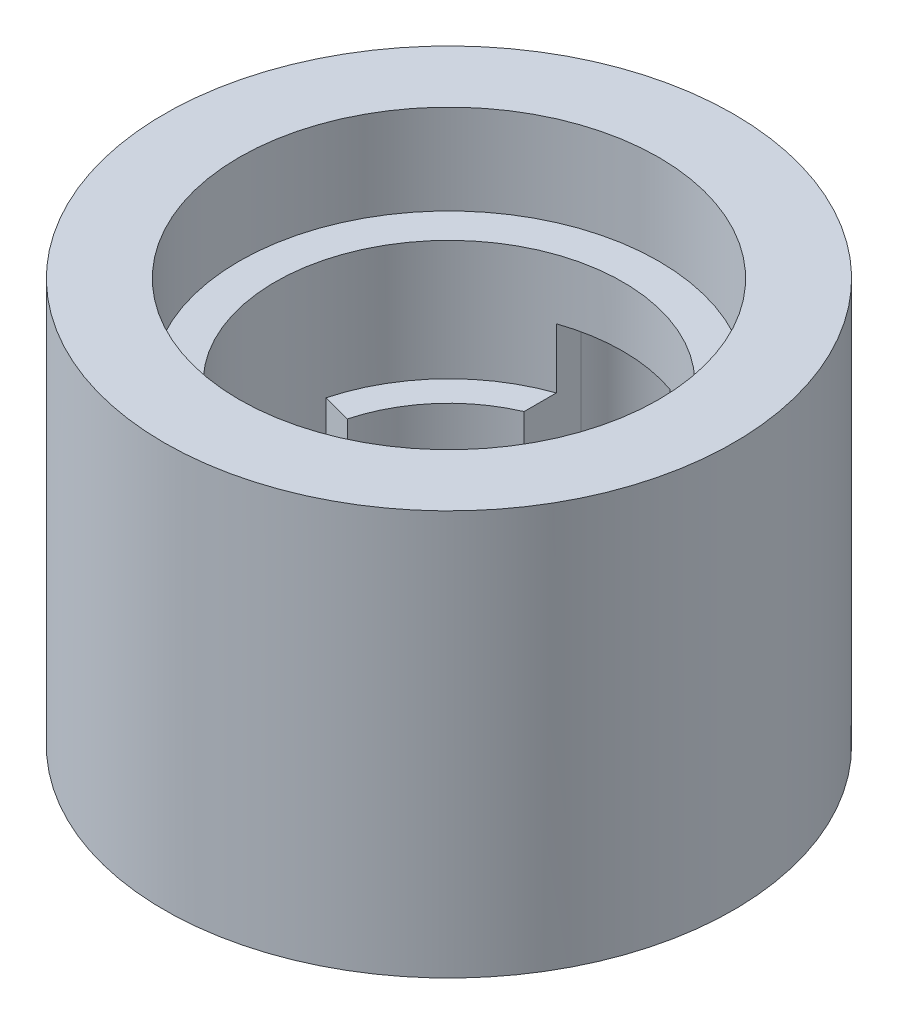
SolidWorks part; units mm, degrees
ref_plane "Front Plane" through (0, 0, 0) normal (0, 0, 1) x (1, 0, 0)
ref_plane "Top Plane" through (0, 0, 0) normal (0, 1, 0) x (1, 0, 0)
ref_plane "Right Plane" through (0, 0, 0) normal (1, 0, 0) x (0, 0, -1)
sketch "Sketch1" plane through (0, 0, 0) normal (0, 1, 0) x (1, 0, 0)
  circle A0 centre (0, 0) radius 12.065
  circle A1 centre (0, 0) radius 7.62
  circle A2 centre (0, 0) radius 6.096
  dimension "D1" = 15.24
  dimension "D2" = 12.192
  dimension "D3" = 24.13
extrude "Boss-Extrude1" add sketch "Sketch1" along normal blind 10.16 contours A1 A2 region at (-7.4045, 0, 0)
extrude "Boss-Extrude2" add sketch "Sketch1<4>" along normal blind 12.7 contours A0 A1 region at (-11.7238, 0, 0)
sketch "Sketch1<4>" plane through (0, 0, 0) normal (0, 1, 0) x (1, 0, 0) same geometry as "Sketch1"
sketch "Sketch9" plane through (0, 12.7, 0) normal (0, 1, 0) x (1, 0, 0)
  circle A0 centre (0, 0) radius 7.62
  circle A1 centre (0, 0) radius 12.065
  circle A2 centre (0, 0) radius 7.62 construction
  circle A3 centre (0, 0) radius 12.065 construction
extrude "Boss-Extrude22" add sketch "Sketch9" along normal blind 1.27
sketch "Sketch10" plane through (0, 13.97, 0) normal (0, 1, 0) x (1, 0, 0)
  circle A0 centre (0, 0) radius 7.62
  circle A1 centre (0, 0) radius 7.62 construction
  circle A2 centre (0, 0) radius 8.89
  dimension "D1" = 1.27
extrude "Cut-Extrude5" cut sketch "Sketch10" against normal up to surface (3.81 mm away) up to face at (0, 10.16, 6.096)
sketch "Sketch14" plane through (0, 0, 0) normal (0, -1, 0) x (1, 0, 0)
  line L0 (6.096, 0) -> (-6.096, 0) construction
  line L1 (2.413, 0) -> (-2.413, 0)
  line L2 (2.413, 0) -> (2.413, -8.001)
  line L3 (2.413, -8.001) -> (-2.413, -8.001)
  line L4 (-2.413, 0) -> (-2.413, -8.001)
  line L5 (0, 0) -> (0, -6.096) construction
  circle A0 centre (0, 0) radius 6.096 construction
  point P4 (0, 0)
  point P10 (0, 0)
  dimension "D1" = 4.826
  dimension "D2" = 1.905
extrude "Cut-Extrude8" cut sketch "Sketch14" against normal offset from surface (7.62 mm away) 2.54 up to face at (0, 10.16, 6.096)
sketch "Sketch15" plane through (0, 7.62, 0) normal (0, -1, 0) x (1, 0, 0)
  line L0 (0, -7.5843) -> (0, -10.033) construction
  line L1 (-2.413, -8.001) -> (2.413, -8.001) construction
  line L2 (2.413, -8.001) -> (-2.413, -8.001)
  arc A0 (2.413, -8.001) -> (-2.413, -8.001) centre (0, -7.5843) cw
  dimension "D1" = 2.032
extrude "Cut-Extrude9" cut sketch "Sketch15" along normal blind 5.08
sketch "Sketch16" plane through (0, 0, 0) normal (0, -1, 0) x (1, 0, 0)
  line L0 (2.413, -5.5981) -> (2.413, -8.001)
  line L1 (2.413, -8.001) -> (-2.413, -8.001)
  line L2 (-2.413, -8.001) -> (-2.413, -5.5981)
  circle A0 centre (0, 0) radius 12.065
  circle A1 centre (0, 0) radius 12.065 construction
  arc A2 (-2.413, -5.5981) -> (2.413, -5.5981) centre (0, 0) cw
  arc A3 (2.413, -5.5981) -> (-2.413, -5.5981) centre (0, 0) ccw construction
extrude "Boss-Extrude24" add sketch "Sketch16" along normal blind 3.175
sketch "Sketch17" plane through (0, 10.16, 0) normal (0, 1, 0) x (1, 0, 0)
  circle A0 centre (0, 0) radius 6.096
  circle A1 centre (0, 0) radius 6.096 construction
  circle A2 centre (0, 0) radius 7.366
  dimension "D1" = 1.27
extrude "Cut-Extrude10" cut sketch "Sketch17" against normal blind 5.08
sketch "Sketch18" plane through (0, 5.08, 0) normal (0, 1, 0) x (1, 0, 0)
  line L0 (0, 0) -> (-7.366, 0) construction
  line L1 (0, 0) -> (-7.115, -1.9065)
  line L2 (0, 0) -> (-7.115, 1.9065)
  arc A0 (-2.413, 6.9596) -> (2.413, 6.9596) centre (0, 0) ccw construction
  arc A1 (-7.115, 1.9065) -> (-7.115, -1.9065) centre (0, 0) ccw
  dimension "D1" = 15
  dimension "D2" = 15
extrude "Cut-Extrude11" cut sketch "Sketch18" against normal up to surface (8.255 mm away) up to face at (0, -3.175, -12.065)
